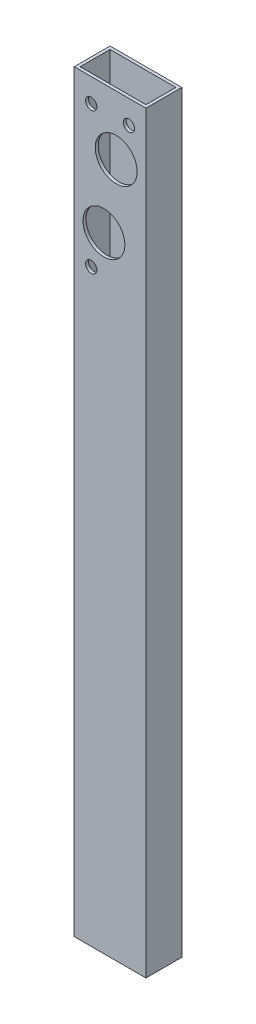
SolidWorks part; units mm, degrees
material "6063-T6"
ref_plane "Front Plane" through (0, 0, 0) normal (0, 0, 1) x (1, 0, 0)
ref_plane "Top Plane" through (0, 0, 0) normal (0, 1, 0) x (1, 0, 0)
ref_plane "Right Plane" through (0, 0, 0) normal (1, 0, 0) x (0, 0, -1)
sketch "Sketch8" plane through (0, 0, 0) normal (0, 0, 1) x (1, 0, 0)
  line L0 (0, 0) -> (0, -50)
  line L1 (0, -50) -> (0, -220)
  line L2 (0, -220) -> (0, -280)
  line L3 (0, 0) -> (0, 520)
  point P3 (0, 0)
  point P7 (0, 0)
  dimension "D1" = 170
  dimension "D2" = 50
  dimension "D3" = 60
  dimension "D4" = 800
sketch "Sketch1" plane through (0, 0, 0) normal (0, 1, 0) x (1, 0, 0)
  line L1 (-38.1, 19.05) -> (38.1, 19.05)
  line L2 (-38.1, 19.05) -> (-38.1, -19.05)
  line L3 (-38.1, -19.05) -> (38.1, -19.05)
  line L4 (38.1, 19.05) -> (38.1, -19.05)
  line L5 (-38.1, 19.05) -> (38.1, -19.05) construction
  line L6 (-38.1, -19.05) -> (38.1, 19.05) construction
  point P0 (0, 0)
  dimension "D1" = 76.2
  dimension "D2" = 38.1
extrude "Extrude-Thin1" add sketch "Sketch1" along normal up to vertex (520 mm away) and the other way up to vertex (280 mm away) thin up to point (0, 520, 0) other way up to point (0, -280, 0) thin type one direction reverse wall 3.175
sketch "Sketch6" plane through (0, 0, 19.05) normal (0, 0, 1) x (1, 0, 0)
  line L2 (-6.5118, 383.0697) -> (6.5118, 456.9303) construction
  line L3 (-38.1, -280) -> (-38.1, 520) construction
  line L6 (0, -440) -> (0, 440) construction
  line L7 (-38.1, 520) -> (38.1, 520) construction
  circle A0 centre (6.5118, 456.9303) radius 22.225
  circle A1 centre (-6.5118, 383.0697) radius 22.225
  point P6 (0, 420)
  dimension "D1" = 44.45
  dimension "D2" = 100
  dimension "D4" = 75
  dimension "D5" = 10
extrude "Cut-Extrude1" cut sketch "Sketch6" against normal up to next
hole_wizard "Ø12.0 (12) Diameter Hole2" positions "Sketch9" profile "Sketch10" hole size "Ø12.0" standard "ANSI Metric" end condition up to next
sketch "Sketch9" plane through (0, 0, 19.05) normal (0, 0, 1) x (1, 0, 0)
  line L0 (-20, 495) -> (20, 495)
  line L4 (0, -440) -> (0, 440) construction
  line L5 (-20, 345) -> (-20, 495)
  line L7 (0, 420) -> (-20, 420)
  line L8 (-6.5118, 383.0697) -> (6.5118, 456.9303) construction
  point P0 (-20, 495)
  point P2 (20, 495)
  point P4 (-20, 345)
  point P23 (0, 495)
  dimension "D1" = 40
  dimension "D2" = 150
sketch "Sketch10" plane through (-20, 495, 19.05) normal (1, 0, 0) x (0, -1, 0)
  line L0 (0, 0) -> (0, 3.175)
  line L1 (0, 3.175) -> (6, 3.175)
  line L2 (6, 3.175) -> (6, 0)
  line L5 (6, 0) -> (0, 0)
  line L11 (0, -6.35) -> (0, 107.95) construction
  dimension "Thru Hole Dia." = 12
  dimension "Thru Hole Depth" = 3.175
hole_wizard "Ø12.0 (12) Diameter Hole1" positions "Sketch2" profile "Sketch3" hole size "Ø12.0" standard "ANSI Metric" end condition up to next
sketch "Sketch2" plane through (0, 0, -19.05) normal (0, 0, -1) x (-1, 0, 0)
  line L1 (-20, -15) -> (20, -15)
  line L2 (-20, -15) -> (-20, -255)
  line L3 (-20, -255) -> (20, -255)
  line L4 (20, -15) -> (20, -255)
  line L5 (0, 440) -> (0, -440) construction
  point P1 (-20, -15)
  point P2 (20, -255)
  point P69 (-20, -255)
  point P70 (20, -15)
  point P71 (0, -255)
  dimension "D1" = 40
  dimension "D2" = 35
  dimension "D3" = 35
sketch "Sketch3" plane through (20, -15, -19.05) normal (1, 0, 0) x (0, 1, 0)
  line L0 (0, 0) -> (0, 3.175)
  line L1 (0, 3.175) -> (6, 3.175)
  line L2 (6, 3.175) -> (6, 0)
  line L5 (6, 0) -> (0, 0)
  line L11 (0, -6.35) -> (0, 107.95) construction
  dimension "Thru Hole Dia." = 12
  dimension "Thru Hole Depth" = 3.175
sketch "Sketch7" plane through (0, 0, -19.05) normal (0, 0, -1) x (-1, 0, 0)
  line L0 (0, 440) -> (0, -440) construction
  circle A0 centre (0, -50) radius 22.225
  circle A1 centre (0, -220) radius 22.225
  dimension "D1" = 44.45
extrude "Cut-Extrude2" cut sketch "Sketch7" against normal up to next
